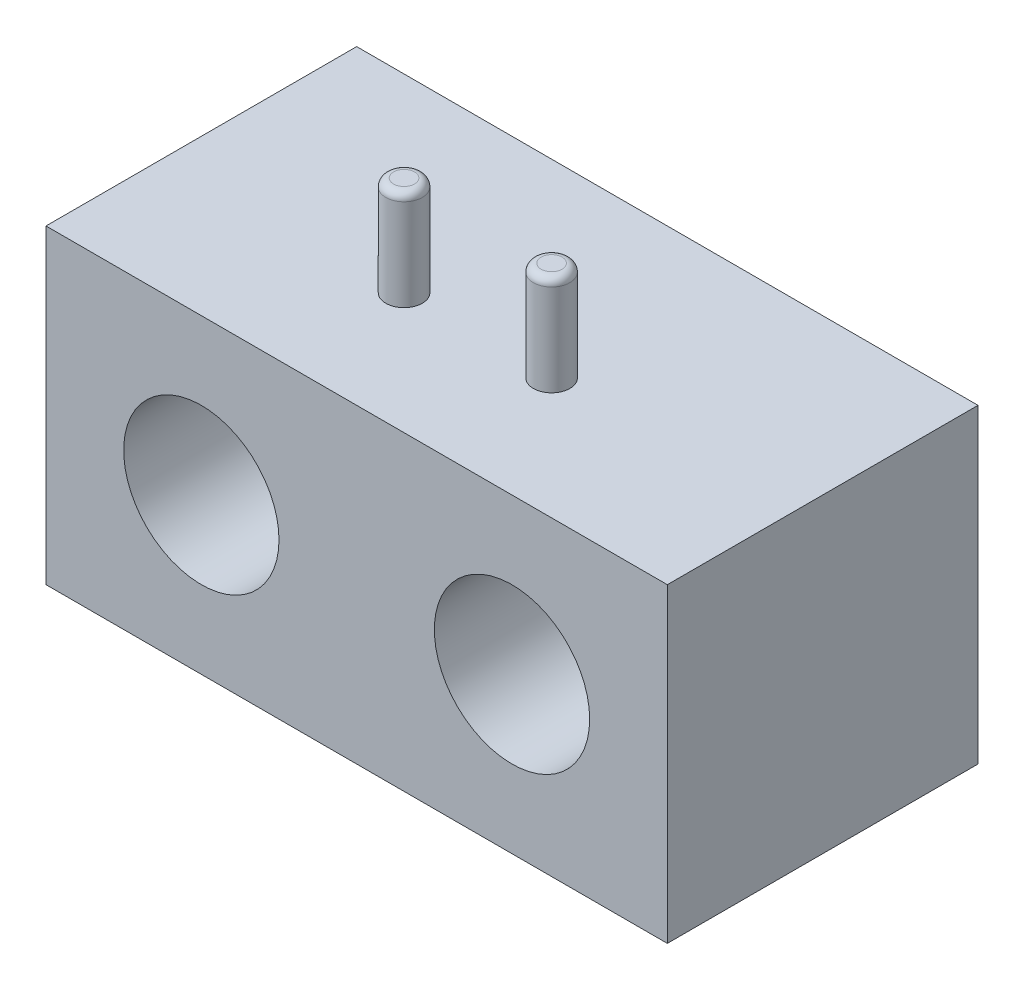
SolidWorks part; units mm, degrees
ref_plane "Front Plane" through (0, 0, 0) normal (0, 0, 1) x (1, 0, 0)
ref_plane "Top Plane" through (0, 0, 0) normal (0, 1, 0) x (1, 0, 0)
ref_plane "Right Plane" through (0, 0, 0) normal (1, 0, 0) x (0, 0, -1)
sketch "Sketch1" plane through (0, 0, 0) normal (0, 0, 1) x (1, 0, 0)
  line L0 (-4.776, 11.36) -> (15.224, 11.36) construction
  line L1 (-14.776, 21.36) -> (25.224, 21.36)
  line L2 (-14.776, 21.36) -> (-14.776, 1.36)
  line L3 (-14.776, 1.36) -> (25.224, 1.36)
  line L4 (25.224, 21.36) -> (25.224, 1.36)
  circle A0 centre (-4.776, 11.36) radius 2.5
  circle A1 centre (15.224, 11.36) radius 2.5
  point P6 (-14.776, 11.36)
  point P9 (5.224, 11.36)
  point P10 (25.224, 11.36)
  point P11 (5.224, 21.36)
  dimension "D3" = 5
  dimension "D4" = 5
  dimension "D5" = 20
  dimension "D1" = 40
  dimension "D2" = 20
extrude "Boss-Extrude1" add sketch "Sketch1" along normal blind 20
sketch "Sketch2" plane through (0, 0, 20) normal (0, 0, 1) x (1, 0, 0)
  circle A0 centre (-4.776, 11.36) radius 5
  circle A1 centre (15.224, 11.36) radius 5
  dimension "D1" = 10
  dimension "D2" = 10
extrude "Cut-Extrude1" cut sketch "Sketch2" against normal offset from surface (18 mm away) 2 up to face at (5.224, 11.36, 0)
sketch "Sketch4" plane through (0, 21.36, 0) normal (0, 1, 0) x (1, 0, 0)
  line L0 (25.224, 0) -> (-14.776, 0) construction
  line L1 (9.974, -12.2) -> (0.474, -12.2) construction
  circle A0 centre (9.974, -12.2) radius 1.175
  circle A1 centre (0.474, -12.2) radius 1.175
  point P4 (5.224, -12.2)
  point P7 (5.224, 0)
  dimension "D1" = 2.35
  dimension "D2" = 2.35
  dimension "D3" = 12.2
  dimension "D4" = 9.5
extrude "Boss-Extrude2" add sketch "Sketch4" along normal blind 6.4
fillet "Fillet1" radius 0.5 2 edges at (0.474, 27.76, 13.375) (9.974, 27.76, 13.375)
